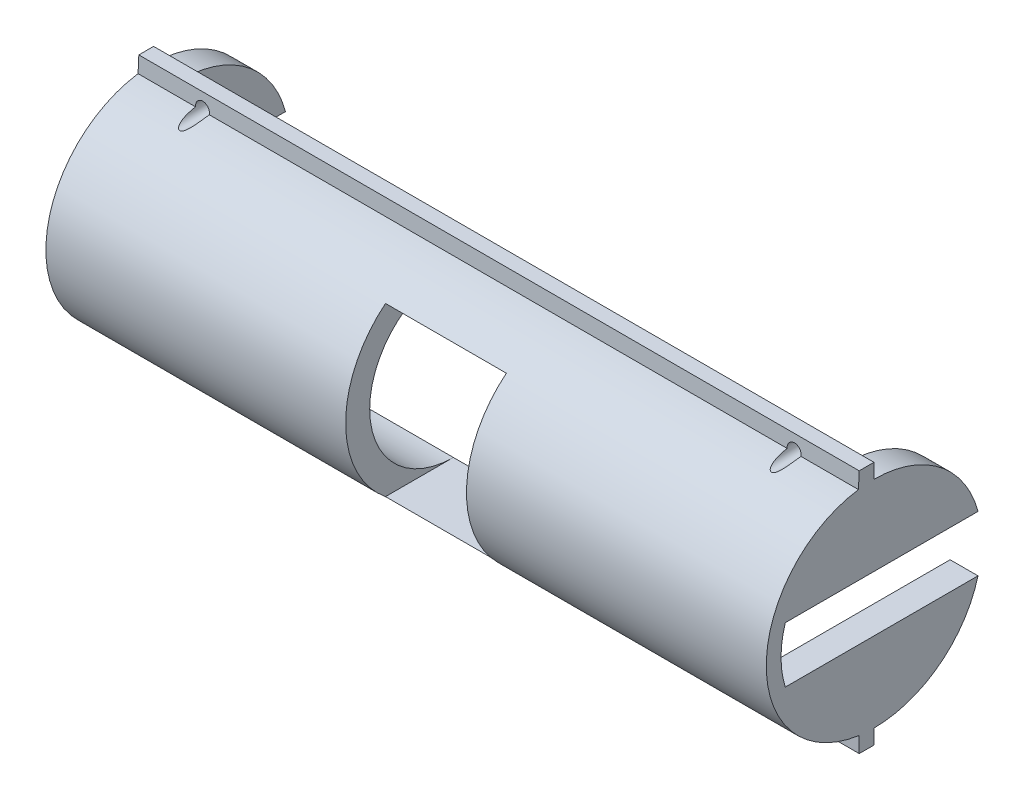
SolidWorks part; units mm, degrees
ref_plane "Front Plane" through (0, 0, 0) normal (0, 0, 1) x (1, 0, 0)
ref_plane "Top Plane" through (0, 0, 0) normal (0, 1, 0) x (1, 0, 0)
ref_plane "Right Plane" through (0, 0, 0) normal (1, 0, 0) x (0, 0, -1)
sketch "Sketch1" plane through (0, 0, 0) normal (1, 0, 0) x (0, 0, -1)
  line L1 (-3.3391, 0) -> (-3.3391, 52.7) construction
  line L10 (-6.5141, 52.7) -> (-6.5141, 0) construction
  line L11 (-6.6781, 49.2832) -> (-6.5141, 52.7)
  line L12 (-6.5141, 52.7) -> (-3.3391, 52.7)
  line L13 (-3.3391, 52.7) -> (-3.3391, 44.35)
  line L14 (-6.5141, 3.3935) -> (-6.5141, 0)
  line L15 (-6.5141, 0) -> (-3.3391, 0)
  line L16 (-3.3391, 0) -> (-3.3391, 8.35)
  arc A2 (-3.3391, 44.35) -> (-3.3391, 8.35) centre (-3.3391, 26.35) ccw
  arc A3 (-6.6781, 49.2832) -> (-6.5141, 3.3935) centre (-3.3391, 26.35) ccw
  dimension "D3" = 23.175
  dimension "D4" = 3.175
  dimension "D2" = 18
  dimension "D1" = 52.7
extrude "Boss-Extrude1" add sketch "Sketch1" along normal blind 155
sketch "Sketch2" plane through (155, 0, 0) normal (1, 0, 0) x (0, 0, -1)
  line L0 (-3.3391, 44.35) -> (-3.3391, 52.7) construction
  line L1 (-3.3391, 0) -> (-3.3391, 8.35) construction
  line L2 (-3.3391, 46.35) -> (-3.3391, 6.35)
  arc A0 (-3.3391, 46.35) -> (-3.3391, 6.35) centre (-3.3391, 26.35) ccw
  dimension "D1" = 20
extrude "Cut-Extrude1" cut sketch "Sketch2" against normal blind 33.5
sketch "Sketch3" plane through (0, 0, 0) normal (-1, 0, 0) x (0, 0, 1)
  line L0 (3.3391, 44.35) -> (3.3391, 52.7) construction
  line L1 (3.3391, 0) -> (3.3391, 8.35) construction
  line L2 (3.3391, 46.35) -> (3.3391, 6.35)
  arc A0 (3.3391, 46.35) -> (3.3391, 6.35) centre (3.3391, 26.35) cw
  dimension "D1" = 20
extrude "Cut-Extrude2" cut sketch "Sketch3" against normal blind 33.5
sketch "Sketch4" plane through (0, 0, 3.3391) normal (0, 0, -1) x (-1, 0, 0)
  line L0 (-77.5, 44.35) -> (-77.5, 8.35) construction
  line L1 (-121.5, 44.35) -> (-33.5, 44.35) construction
  line L2 (-121.5, 8.35) -> (-33.5, 8.35) construction
  line L3 (-155, 26.35) -> (0, 26.35) construction
  line L4 (-155, 46.35) -> (-155, 6.35) construction
  line L5 (0, 6.35) -> (0, 46.35) construction
  line L7 (-90.5, 8.35) -> (-64.5, 8.35)
  line L8 (-90.5, 8.35) -> (-90.5, 44.35)
  line L9 (-90.5, 44.35) -> (-64.5, 44.35)
  line L10 (-64.5, 8.35) -> (-64.5, 44.35)
  line L11 (-90.5, 8.35) -> (-64.5, 44.35) construction
  line L12 (-90.5, 44.35) -> (-64.5, 8.35) construction
  point P12 (-77.5, 26.35)
  dimension "D1" = 26
extrude "Cut-Extrude3" cut sketch "Sketch4" against normal through all both and the other way through all
sketch "Sketch5" plane through (0, 0, 3.3391) normal (0, 0, -1) x (-1, 0, 0)
  line L0 (-155, 49.525) -> (0, 49.525) construction
  line L1 (-155, 46.35) -> (-155, 52.7) construction
  line L2 (0, 46.35) -> (0, 52.7) construction
  line L3 (-155, 3.175) -> (0, 3.175) construction
  line L4 (-155, 0) -> (-155, 6.35) construction
  line L5 (0, 0) -> (0, 6.35) construction
  circle A0 centre (-141.15, 49.525) radius 1.5
  circle A1 centre (-141.15, 3.175) radius 1.5
  circle A2 centre (-13.85, 49.525) radius 1.5
  circle A3 centre (-13.85, 3.175) radius 1.5
  dimension "D5" = 3
  dimension "D6" = 3
  dimension "D7" = 3
  dimension "D8" = 3
  dimension "D1" = 13.85
  dimension "D2" = 13.85
  dimension "D3" = 13.85
  dimension "D4" = 13.85
extrude "Cut-Extrude4" cut sketch "Sketch5" against normal through all both and the other way through all
sketch "Sketch6" plane through (155, 0, 0) normal (1, 0, 0) x (0, 0, -1)
  line L0 (-26.5139, 26.2671) -> (-3.3391, 26.35) construction
  line L1 (-3.3391, 20.35) -> (-25.7239, 20.35) construction
  line L2 (-3.3391, 32.35) -> (-25.7239, 32.35) construction
  line L3 (-3.3391, 32.35) -> (36.9329, 32.35) construction
  line L4 (-3.3391, 20.35) -> (36.9329, 20.35) construction
  line L5 (-25.7239, 32.35) -> (19.0458, 32.35)
  line L6 (-25.7239, 20.35) -> (19.0458, 20.35)
  arc A0 (-6.6781, 49.2832) -> (-6.5141, 3.3935) centre (-3.3391, 26.35) ccw construction
  arc A1 (-25.7239, 32.35) -> (19.0458, 32.35) centre (-3.3391, 26.35) cw
  arc A2 (-25.7239, 20.35) -> (19.0458, 20.35) centre (-3.3391, 26.35) ccw
  dimension "D1" = 6
  dimension "D2" = 6
extrude "Boss-Extrude2" add sketch "Sketch6" against normal blind 6
ref_axis "Axis1" through (77.5, 44.35, 17.9363) along (0, -1, 0)
ref_plane "Plane1" through (77.5, 0, 0) normal (1, 0, 0) x (0, 0, -1)
mirror "Mirror1" about plane through (77.5, 0, 0) normal (1, 0, 0) of "Boss-Extrude2"
